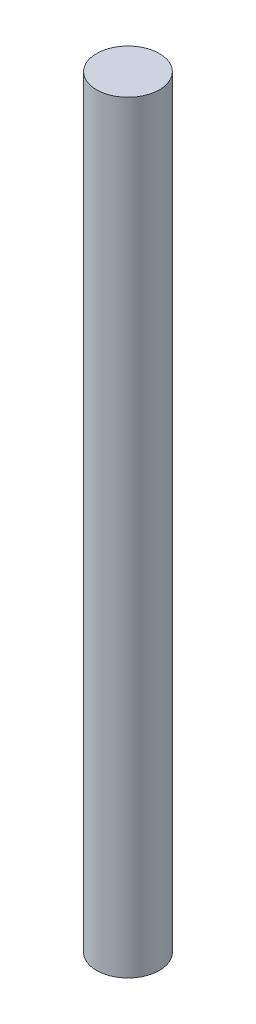
SolidWorks part; units mm, degrees
ref_plane "Front Plane" through (0, 0, 0) normal (0, 0, 1) x (1, 0, 0)
ref_plane "Top Plane" through (0, 0, 0) normal (0, 1, 0) x (1, 0, 0)
ref_plane "Right Plane" through (0, 0, 0) normal (1, 0, 0) x (0, 0, -1)
sketch "Elevation Bar" plane through (0, 0, 0) normal (0, 1, 0) x (1, 0, 0)
  circle A0 centre (0, 0) radius 30.226
  dimension "D1" = 60.452
extrude "Elevation Bar Part" add sketch "Elevation Bar" along normal blind 734.06
sketch "Sketch2" plane through (0, 0, 0) normal (0, 0, 1) x (1, 0, 0)
  line L0 (0, 0) -> (172.1794, 0) construction
  line L1 (-30.226, 0) -> (-30.226, 734.06) construction
  line L2 (-30.226, 734.06) -> (30.226, 734.06) construction
  line L3 (30.226, 734.06) -> (30.226, 0) construction
  line L4 (30.226, 0) -> (30.226, 734.06) construction
  line L5 (636.651, 40.7185) -> (27.051, 40.7185) construction
  line L6 (636.651, 53.4185) -> (27.051, 53.4185)
  line L7 (636.651, 53.4185) -> (636.651, 28.0185)
  line L8 (636.651, 28.0185) -> (27.051, 28.0185)
  line L9 (27.051, 53.4185) -> (27.051, 28.0185)
  circle A0 centre (576.5632, 40.7185) radius 41.275 construction
  circle A1 centre (87.1388, 40.7185) radius 41.275 construction
  circle A2 centre (331.851, 40.7185) radius 41.275 construction
  point P24 (331.851, 40.7185)
  dimension "D2" = 82.55
  dimension "D1" = 609.6
  dimension "D3" = 25.4
  dimension "D4" = 244.7122
  dimension "D5" = 244.7122
sketch "Sketch4" plane through (0, 0, 0) normal (0, 0, 1) x (1, 0, 0)
  line L0 (-30.226, 164.5435) -> (-30.226, 81.9935) construction
  line L1 (52.451, 81.9935) -> (27.051, 81.9935) construction
  line L2 (-30.226, 0) -> (-30.226, 734.06) construction
  line L3 (30.226, 734.06) -> (30.226, 0) construction
  line L4 (-30.226, 164.5435) -> (30.226, 81.9935) construction
  line L5 (30.226, 81.9935) -> (-30.226, 81.9935) construction
  line L6 (27.051, 81.9935) -> (-30.226, 164.5435) construction
  line L7 (27.051, 81.9935) -> (27.051, 40.7185) construction
  line L8 (30.226, 226.8605) -> (203.668, 53.4185) construction
  line L11 (636.651, 53.4185) -> (27.051, 53.4185) construction
  circle A0 centre (52.451, 81.9935) radius 20.6375
  circle A1 centre (52.451, 81.9935) radius 25.4
  circle A2 centre (52.451, 81.9935) radius 22.225 construction
  circle A3 centre (-46.488, 164.5435) radius 16.262
  circle A4 centre (81.026, 104.2185) radius 50.8 construction
  dimension "D1" = 50.8
  dimension "D2" = 41.275
  dimension "D3" = 1.5875
  dimension "D4" = 3.175
  dimension "D5" = 82.55
  dimension "D8" = 101.6
  dimension "D6" = 53.784
  dimension "D7" = 55.245
  dimension "D9" = 45
ref_plane "Plane1" through (0, 53.4185, 0) normal (0, 1, 0) x (1, 0, 0)
equation "\"D5@Sketch2\"=\"D4@Sketch2\""
